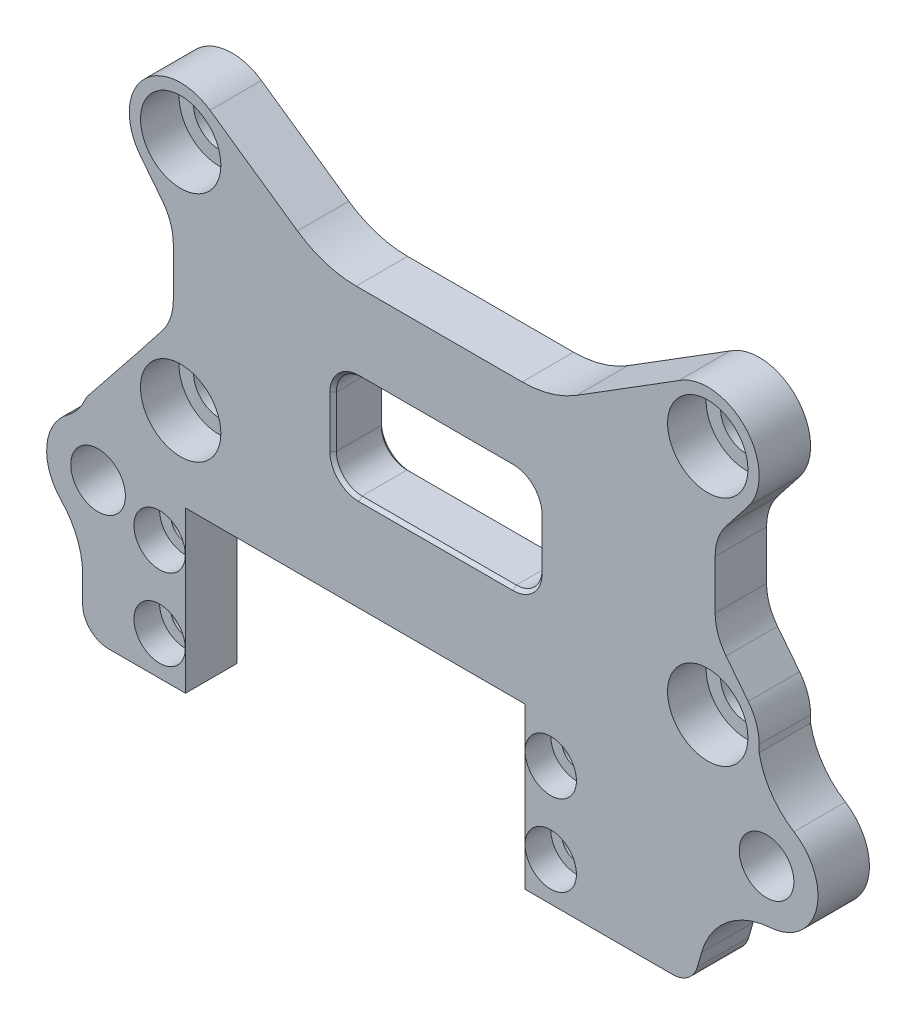
SolidWorks part; units mm, degrees
ref_plane "Front Plane" through (0, 0, 0) normal (0, 0, 1) x (1, 0, 0)
ref_plane "Top Plane" through (0, 0, 0) normal (0, 1, 0) x (1, 0, 0)
ref_plane "Right Plane" through (0, 0, 0) normal (1, 0, 0) x (0, 0, -1)
sketch "Sketch1" plane through (0, 0, 0) normal (0, 0, 1) x (1, 0, 0)
  line L0 (-18.8232, 25.0598) -> (-18.8232, -3.6422) construction
  line L1 (46.2643, -3.6422) -> (46.2643, 25.0598) construction
  line L2 (46.2643, 10.7088) -> (-18.8232, 10.7088) construction
  line L3 (-19.7352, 15.9265) -> (-23.8222, 21.1441)
  line L4 (-1.1351, 20.4907) -> (-15.197, 30.2726)
  line L5 (13.7205, 10.7088) -> (13.7205, 0) construction
  line L6 (26.9887, 20.4907) -> (42.6381, 30.2726)
  line L7 (47.1763, 15.9265) -> (51.2633, 21.1441)
  line L8 (-1.1351, 20.4907) -> (26.9887, 20.4907)
  line L9 (47.1763, 5.4912) -> (51.2633, 0.2735)
  line L10 (-19.7352, 5.4912) -> (-23.8222, 0.2735)
  line L11 (-19.7352, 15.9265) -> (-19.7352, 5.4912)
  line L12 (47.1763, 15.9265) -> (47.1763, 5.4912)
  line L13 (-25.1732, -3.6422) -> (-25.1732, -37.6595)
  line L14 (-25.1732, -37.6595) -> (52.6143, -37.6595)
  line L15 (52.6143, -3.6422) -> (52.6143, -37.6595)
  circle A0 centre (-18.8232, 25.0598) radius 3.175
  circle A1 centre (46.2643, 25.0598) radius 3.175
  arc A2 (-15.197, 30.2726) -> (-23.8222, 21.1441) centre (-18.8232, 25.0598) ccw
  arc A3 (51.2633, 21.1441) -> (42.6381, 30.2726) centre (46.2643, 25.0598) ccw
  arc A4 (52.6143, -3.6422) -> (51.2633, 0.2735) centre (46.2643, -3.6422) ccw
  circle A5 centre (46.2643, -3.6422) radius 3.175
  circle A6 centre (-18.8232, -3.6422) radius 3.175
  arc A7 (-23.8222, 0.2735) -> (-25.1732, -3.6422) centre (-18.8232, -3.6422) ccw
  dimension "D1" = 6.35
  dimension "D4" = 12.7
  dimension "D3" = 2
  dimension "D6" = 28.702
  dimension "D7" = 65.0875
  dimension "D2" = 2
  dimension "D5" = 2
extrude "Boss-Extrude1" add sketch "Sketch1" along normal blind 6.35
fillet "Fillet1" radius 6.35 4 edges at (-19.7352, 15.9265, 3.175) (-19.7352, 5.4912, 3.175) (47.1763, 15.9265, 3.175) (47.1763, 5.4912, 3.175)
fillet "Fillet2" radius 12.7 2 edges at (26.9887, 20.4907, 3.175) (-1.1351, 20.4907, 3.175)
sketch "Sketch2" plane through (0, 0, 6.35) normal (0, 0, 1) x (1, 0, 0)
  circle A0 centre (-18.8232, 25.0598) radius 4.9625
  circle A1 centre (-18.8232, -3.6422) radius 4.9625
  circle A2 centre (46.2643, -3.6422) radius 4.9625
  circle A3 centre (46.2643, 25.0598) radius 4.9625
  dimension "D1" = 9.925
  dimension "D2" = 9.925
  dimension "D3" = 9.925
  dimension "D4" = 9.925
extrude "Cut-Extrude1" cut sketch "Sketch2" against normal blind 4.7625
sketch "Sketch5" plane through (0, 0, 0) normal (0, 0, -1) x (-1, 0, 0)
  line L1 (-2.7263, 20.4907) -> (-2.7263, -37.6595) construction
  line L2 (-47.1763, 7.6821) -> (-47.1763, 13.7355) construction
  circle A0 centre (21.4237, -18.8138) radius 1.778
  circle A1 centre (21.4237, -28.8138) radius 1.778
  circle A2 centre (-26.8762, -28.8138) radius 1.778
  circle A3 centre (-26.8762, -18.8138) radius 1.778
  dimension "D1" = 3.556
  dimension "D2" = 3.556
  dimension "D3" = 24.1499
  dimension "D4" = 44.45
  dimension "D5" = 24.1499
  dimension "D8" = 10
extrude "Cut-Extrude3" cut sketch "Sketch5" against normal through all
sketch "Sketch6" plane through (0, 0, 6.35) normal (0, 0, 1) x (1, 0, 0)
  line L0 (-25.1732, -3.6422) -> (-25.1732, -37.6595)
  line L1 (-25.1732, -3.6422) -> (-25.1732, -37.6595) construction
  line L2 (44.3171, -33.5955) -> (54.4579, 1.9274)
  line L3 (-25.1732, -37.6595) -> (52.6143, -37.6595) construction
  line L4 (-25.1732, -33.5955) -> (-18.2287, -33.5955)
  line L5 (23.6813, -13.7835) -> (23.6813, -33.5955)
  line L6 (33.8818, -37.6595) -> (-8.0282, -37.6595)
  line L7 (-18.2287, -13.7835) -> (-18.2287, -33.5955)
  line L8 (33.8818, -12.2595) -> (-8.0282, -37.6595) construction
  line L9 (33.8818, -37.6595) -> (-8.0282, -12.2595) construction
  line L10 (-25.1732, -33.5955) -> (-25.1732, -3.6422)
  line L11 (-25.1732, -37.6595) -> (-17.5532, -37.6595)
  line L12 (51.0268, -37.6595) -> (43.4068, -37.6595)
  line L13 (51.0268, -37.6595) -> (52.6143, -37.6595)
  line L14 (52.6143, -37.6595) -> (54.4579, 1.9274)
  line L15 (23.6813, -33.5955) -> (44.3171, -33.5955)
  line L16 (-21.4237, -18.8138) -> (26.8762, -18.8138) construction
  line L17 (2.7263, -18.8138) -> (2.7263, -37.6595) construction
  line L18 (-18.2287, -13.7835) -> (23.6813, -13.7835)
  line L19 (2.7263, -13.7835) -> (2.7263, -33.5955) construction
  circle A0 centre (46.2643, -3.6422) radius 6.35
  point P6 (12.9268, -24.9595)
  line M31 (-25.1732, -3.6422) -> (-25.1732, -37.6595)
  line M32 (-25.1732, -37.6595) -> (52.6143, -37.6595)
  line M33 (52.6143, -37.6595) -> (52.6143, -3.6422)
  dimension "D1" = 25.4
  dimension "D2" = 41.91
  dimension "D3" = 4.064
extrude "Cut-Extrude15" cut sketch "Sketch6" against normal through all contours L18 L7 L4 L10 L15 L5 M31 M32 M33 region at (9.9538, -26.6888, 6.35)
sketch "Sketch11" plane through (0, 0, 6.35) normal (0, 0, 1) x (1, 0, 0)
  line L0 (2.7263, -13.7835) -> (2.7263, -33.5955) construction
  line L1 (-18.2287, -13.7835) -> (23.6813, -13.7835) construction
  circle A0 centre (-21.4237, -18.8138) radius 3.1702
  circle A1 centre (-21.4237, -28.8138) radius 3.1702
  circle A2 centre (26.8762, -28.8138) radius 3.1702
  circle A3 centre (26.8762, -18.8138) radius 3.1702
  dimension "D1" = 6.3404
  dimension "D2" = 6.3404
  dimension "D3" = 6.3404
  dimension "D4" = 6.3404
  dimension "D5" = 24.1499
  dimension "D6" = 24.1499
  dimension "D7" = 24.1499
  dimension "D8" = 24.1499
extrude "Cut-Extrude16" cut sketch "Sketch11" against normal blind 3.175
sketch "Sketch13" plane through (0, 0, 6.35) normal (0, 0, 1) x (1, 0, 0)
  line L0 (-25.1732, -33.5955) -> (-30.9287, -33.5955)
  line L1 (-30.9287, -33.5955) -> (-30.9287, -8.6329)
  line L2 (-30.9287, -8.6329) -> (-23.8046, 0.2959)
  line L3 (-18.2287, -13.7835) -> (-18.2287, -33.5955) construction
  line L4 (-21.0862, 3.7664) -> (-23.8222, 0.2735) construction
  line L10 (-23.8046, 0.2959) -> (-23.8222, 0.2735)
  line L11 (-25.1732, -3.6422) -> (-25.1732, -33.5955)
  arc A0 (-23.8222, 0.2735) -> (-25.1732, -3.6422) centre (-18.8232, -3.6422) ccw construction
  arc A1 (-23.8222, 0.2735) -> (-25.1732, -3.6422) centre (-18.8232, -3.6422) ccw
  point P8 (-18.2287, -23.6895)
  line M30 (-21.0862, 3.7664) -> (-23.8222, 0.2735)
  arc M31 (-23.8222, 0.2735) -> (-25.1732, -3.6422) centre (-18.8232, -3.6422) ccw
  line M32 (-25.1732, -3.6422) -> (-25.1732, -33.5955)
  dimension "D1" = 12.7
extrude "Boss-Extrude2" add sketch "Sketch13" against normal up to surface (6.35 mm away) contours L2 L1 L0 M32 M31 M30 region at (-27.92, -19.1772, 6.35) up to face at (49.4393, -3.6422, 0)
sketch "Sketch12" plane through (0, 0, 6.35) normal (0, 0, 1) x (1, 0, 0)
  line L0 (-19.7352, 10.7088) -> (47.1763, 10.7088) construction
  line L1 (-19.7352, 13.7355) -> (-19.7352, 7.6821) construction
  line L2 (47.1763, 7.6821) -> (47.1763, 13.7355) construction
  line L4 (0, 10.7088) -> (25.4, 10.7088)
  line L5 (0, 10.7088) -> (0, -1.9912)
  line L6 (0, -1.9912) -> (25.4, -1.9912)
  line L7 (25.4, 10.7088) -> (25.4, -1.9912)
  dimension "D1" = 25.4
  dimension "D2" = 12.7
extrude "Cut-Extrude17" cut sketch "Sketch12" against normal through all
fillet "Fillet14" radius 3.175 4 edges at (25.4, 10.7088, 3.175) (0, 10.7088, 3.175) (0, -1.9912, 3.175) (25.4, -1.9912, 3.175)
chamfer "Chamfer4" distance 0.4 angle 45 16 edges at (24.4701, -1.0612, 0) (25.4, 4.3588, 0) (24.4701, 9.7789, 0) (12.7, 10.7088, 0) (0.9299, 9.7789, 0) (0, 4.3588, 0) (0.9299, -1.0612, 0) (12.7, -1.9912, 0) (24.4701, -1.0612, 6.35) (25.4, 4.3588, 6.35) (24.4701, 9.7789, 6.35) (12.7, -1.9912, 6.35) (0.9299, -1.0612, 6.35) (0, 4.3588, 6.35) (0.9299, 9.7789, 6.35) (12.7, 10.7088, 6.35)
fillet "Fillet16" radius 3.175 2 edges at (-30.9287, -8.6329, 3.175) (-30.9287, -33.5955, 3.175)
fillet "Fillet17" radius 3.175 1 edges at (44.3171, -33.5955, 3.175)
sketch "Sketch16" plane through (0, 0, 6.35) normal (0, 0, 1) x (1, 0, 0)
  line L0 (-29.0237, -16.2144) -> (53.5263, -16.2144) construction
  line L1 (2.7263, -13.7835) -> (2.7263, -33.3158) construction
  line L2 (-18.2287, -13.7835) -> (23.6813, -13.7835) construction
  line L3 (53.5263, -9.8644) -> (51.0917, -9.8644)
  line L4 (44.9747, -31.292) -> (52.6143, -4.5308) construction
  line L5 (53.5263, -22.5644) -> (47.4662, -22.5644)
  line L6 (47.4662, -22.5644) -> (48.2643, -19.7688)
  line L7 (51.0917, -9.8644) -> (50.9337, -10.4177)
  circle A0 centre (-29.0237, -16.2144) radius 3.375
  circle A1 centre (53.5263, -16.2144) radius 3.375
  arc A2 (-22.6813, -15.9037) -> (-24.2001, -20.3441) centre (-29.0237, -16.2144) ccw
  arc A3 (50.9337, -10.4177) -> (48.2643, -19.7688) centre (53.5263, -16.2144) ccw
  arc A4 (53.5263, -22.5644) -> (53.5263, -9.8644) centre (53.5263, -16.2144) ccw
  circle A7 centre (-21.4237, -18.8138) radius 3.1702 construction
  arc A8 (-22.6813, -15.9037) -> (-24.2001, -20.3441) centre (-21.4237, -18.8138) ccw
  dimension "D1" = 6.75
  dimension "D2" = 6.75
  dimension "D5" = 12.7
  dimension "D6" = 12.7
  dimension "D3" = 50.8
  dimension "D4" = 82.55
extrude "Boss-Extrude4" add sketch "Sketch16" against normal up to surface (6.35 mm away) up to face at (12.7, 4.3588, 0)
sketch "Sketch17" plane through (0, 0, 6.35) normal (0, 0, 1) x (1, 0, 0)
  circle A0 centre (-29.0237, -16.2144) radius 3.375
extrude "Cut-Extrude19" cut sketch "Sketch17" against normal through all
fillet "Fillet19" radius 6.35 1 edges at (-30.9287, -10.1569, 3.175)
fillet "Fillet20" radius 9.525 3 edges at (47.4662, -22.5644, 3.175) (51.0917, -9.8644, 3.175) (-30.9287, -22.2719, 3.175)
